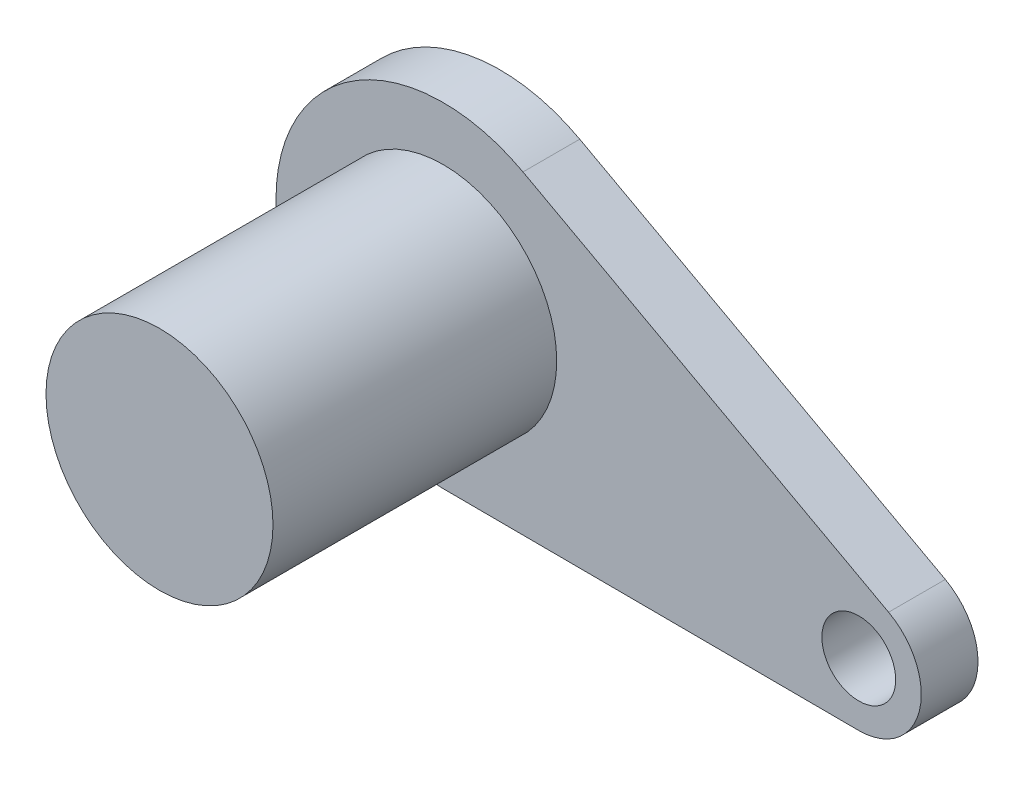
SolidWorks part; units mm, degrees
ref_plane "Front Plane" through (0, 0, 0) normal (0, 0, 1) x (1, 0, 0)
ref_plane "Top Plane" through (0, 0, 0) normal (0, 1, 0) x (1, 0, 0)
ref_plane "Right Plane" through (0, 0, 0) normal (1, 0, 0) x (0, 0, -1)
sketch "Sketch1" plane through (0, 0, 0) normal (0, 0, 1) x (1, 0, 0)
  circle A0 centre (30.4583, 35.7329) radius 2
  dimension "D1" = 4
extrude "Boss-Extrude1" add sketch "Sketch1" against normal blind 5
sketch "Sketch2" plane through (0, 0, -5) normal (0, 0, -1) x (-1, 0, 0)
  line L0 (-6.6075, 4.3687) -> (-37.7818, 33.8572) construction
  line L2 (-6.6075, 4.3687) -> (-6.6075, 3.1275) construction
  line L3 (13.0927, 3.1275) -> (-10.268, 3.1275) construction
  line L4 (-30.4462, 32.7862) -> (-37.7818, 32.7562)
  line L5 (-38.3071, 34.8248) -> (-31.8643, 38.3226)
  circle A0 centre (-37.7818, 33.8572) radius 1.101
  circle A1 centre (-30.4583, 35.7329) radius 2.9468
  parabola Q0 (-3.3135, 7.6184) -> (-5.96, 4.7597) focus (-7.359, 8.7767) apex (-4.3975, 6.0986) construction
  circle M4 centre (-30.4583, 35.7329) radius 2
extrude "Boss-Extrude2" add sketch "Sketch2" along normal blind 1 contours A0 | A1 L5 A0 L4 | A1 M4 | M4 region at (37.7818, 33.8572, -5) region at (34.7414, 34.6359, -5) region at (33.2322, 35.0225, -5) region at (30.4583, 35.7329, -5)
sketch "Sketch3" plane through (0, 0, -5) normal (0, 0, 1) x (1, 0, 0)
  circle A0 centre (37.7818, 33.8572) radius 0.65
  dimension "D1" = 1.3
extrude "Cut-Extrude1" cut sketch "Sketch3" against normal through all both and the other way through all
